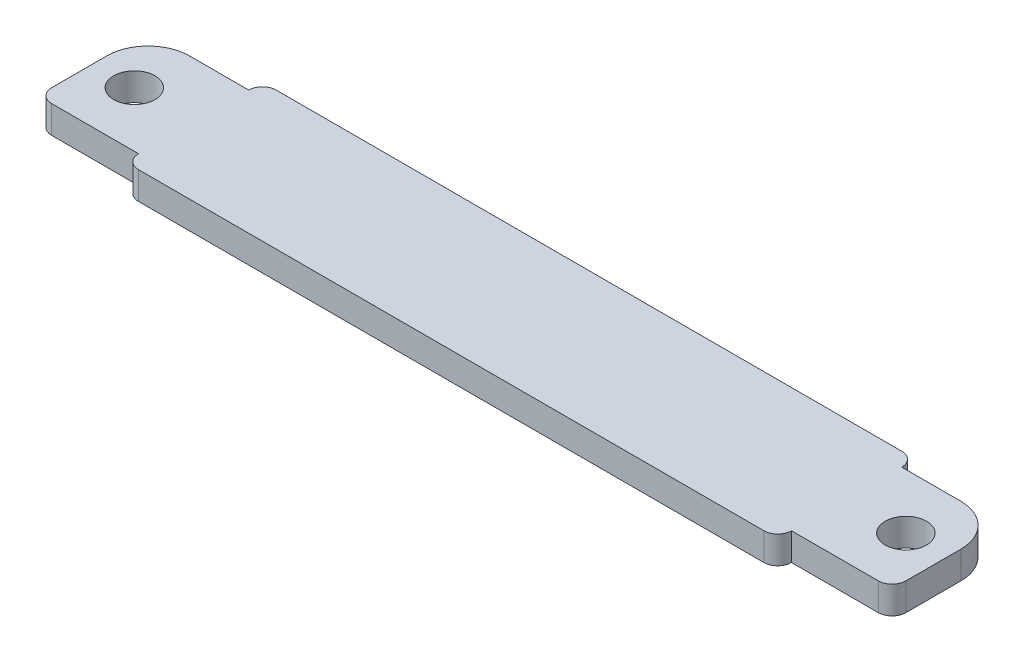
SolidWorks part; units mm, degrees
ref_plane "Спереди" through (0, 0, 0) normal (0, 0, 1) x (1, 0, 0)
ref_plane "Сверху" through (0, 0, 0) normal (0, 1, 0) x (1, 0, 0)
ref_plane "Справа" through (0, 0, 0) normal (1, 0, 0) x (0, 0, -1)
sketch "Sketch1" plane through (0, 0, 0) normal (0, 1, 0) x (1, 0, 0)
  line L0 (-28.05, 0) -> (27.95, 0) construction
  line L1 (-23.75, 5) -> (23.65, 5)
  line L2 (-23.75, 5) -> (-23.75, 4)
  line L3 (-23.75, -5) -> (23.65, -5)
  line L4 (23.65, 5) -> (23.65, 4)
  line L5 (-23.75, 5) -> (23.65, -5) construction
  line L6 (-23.75, -5) -> (23.65, 5) construction
  line L7 (-23.75, -4) -> (-23.75, -5)
  line L8 (-31.05, 4) -> (-23.75, 4)
  line L9 (-31.05, 4) -> (-31.05, -4)
  line L10 (-31.05, -4) -> (-23.75, -4)
  line L11 (23.65, -4) -> (23.65, -5)
  line L12 (30.95, 1) -> (30.95, -5) construction
  line L13 (-31.05, -5) -> (-31.05, 1) construction
  line L14 (30.95, 4) -> (23.65, 4)
  line L15 (30.95, 4) -> (30.95, -4)
  line L16 (30.95, -4) -> (23.65, -4)
  line L17 (-23.75, -5) -> (-23.75, 10.7) construction
  line L18 (23.65, 10.7) -> (23.65, -5) construction
  circle A0 centre (-28.05, 0) radius 1.5
  circle A1 centre (27.95, 0) radius 1.5
  circle A2 centre (-28.05, 0) radius 1.55 construction
  point P0 (-0.05, 0)
  point P9 (-0.05, 0)
  dimension "D1" = 3
  dimension "D2" = 1
  dimension "D3" = 1
  dimension "D4" = 10
extrude "Boss-Extrude1" add sketch "Sketch1" along normal blind 2
fillet "Fillet1" radius 3 2 edges at (-31.05, 1, -4) (30.95, 1, -4)
fillet "Fillet2" radius 1 6 edges at (-23.75, 1, 5) (23.65, 1, 5) (23.65, 1, -5) (-23.75, 1, -5) (-31.05, 1, 4) (30.95, 1, 4)
